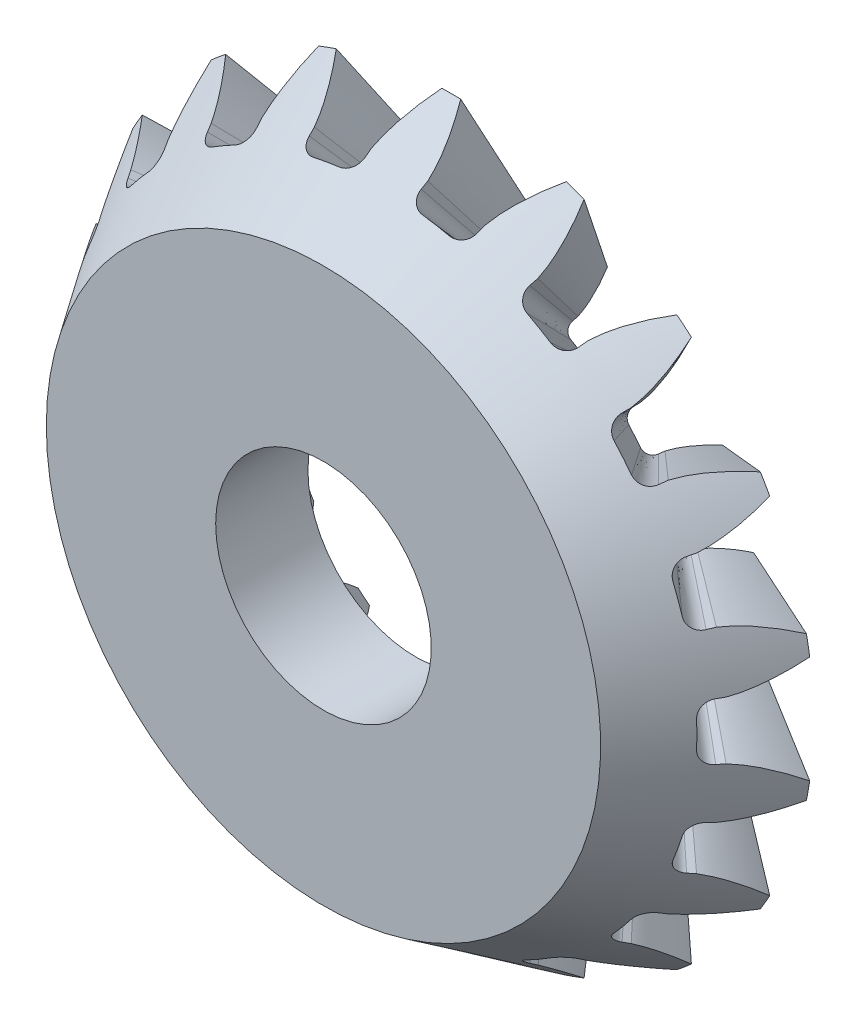
SolidWorks part; units mm, degrees
ref_plane "Front Plane" through (0, 0, 0) normal (0, 0, 1) x (1, 0, 0)
ref_plane "Top Plane" through (0, 0, 0) normal (0, 1, 0) x (1, 0, 0)
ref_plane "Right Plane" through (0, 0, 0) normal (1, 0, 0) x (0, 0, -1)
ref_axis "Gear Axis" through (0, 0, -1.3521) along (0, 0, 1)
sketch "Blank Sketch" plane through (0, 0, 0) normal (0, 1, 0) x (1, 0, 0)
  line L0 (0, 0) -> (0, -27.0416) construction
  line L1 (0, 0) -> (22.5, -15) construction
  line L2 (0, 0) -> (15.0115, -10.0077) construction
  line L3 (11.176, -15.7611) -> (15.6135, -9.1047)
  line L4 (15.6135, -9.1047) -> (23.5324, -13.4515)
  line L5 (23.5324, -13.4515) -> (17.9981, -21.7528)
  line L6 (17.9981, -21.7528) -> (7, -21.7528)
  line L7 (7, -21.7528) -> (7, -15.7611)
  line L8 (7, -15.7611) -> (11.176, -15.7611)
  line L9 (22.5, -15) -> (23.5324, -13.4515) construction
  line L10 (22.5, -15) -> (17.9981, -21.7528) construction
  line L11 (15.0115, -10.0077) -> (11.176, -15.7611) construction
  dimension "Axis" = 27.0416
  dimension "Cone" = 56.31
  dimension "Heel" = 27.0416
  dimension "Toe Cone" = 56.31
  dimension "Toe" = 18.0416
  dimension "Heel Square" = 90
  dimension "Addendum" = 1.8611
  dimension "Root Square" = 90
  dimension "Heel Rim" = 8.1158
  dimension "Toe Square" = 90
  dimension "Toe Rim" = 6.9147
  dimension "Front Square" = 90
  dimension "Face" = 4.927
  dimension "Back" = 10.9981
  dimension "Front" = 4.176
revolve "Blank" add sketch "Blank Sketch" angle 360 about L0
sketch "Cone Sketch" plane through (0, 0, 0) normal (0, 1, 0) x (1, 0, 0)
  line L0 (0, 0) -> (0, -27.0416) construction
  line L1 (0, 0) -> (24.5801, -16.3868)
  line L2 (0, 0) -> (12.9314, -8.6209)
  dimension "Axis" = 27.0416
  dimension "Toe Cone" = 56.31
  dimension "Heel Cone" = 56.31
  dimension "Heel" = 29.5416
  dimension "Toe" = 15.5416
ref_plane "Heel Plane" through (24.5801, 0, 16.3868) normal (0.8321, 0, 0.5547) x (0.5547, 0, -0.8321)
ref_plane "Toe Plane" through (12.9314, 0, 8.6209) normal (0.8321, 0, 0.5547) x (0.5547, 0, -0.8321)
sketch "Heel Section Sketch" plane through (24.5801, 0, 16.3868) normal (0.8321, 0, 0.5547) x (0.5547, 0, -0.8321)
  line L0 (0, 0) -> (-44.3125, 0) construction
  line L1 (-2.4361, 2.0543) -> (-2.9674, 2.0282)
  line L2 (-2.4361, -2.0543) -> (-2.9674, -2.0282)
  line L3 (4.4427, 5.6087) -> (4.4427, -5.6087)
  arc A0 (-2.9674, 2.0282) -> (-3.9541, 0.9668) centre (-2.9166, 0.9916) ccw
  arc A1 (-3.9541, -0.9668) -> (-2.9674, -2.0282) centre (-2.9166, -0.9916) ccw
  arc A2 (-3.9541, -0.9668) -> (-3.9541, 0.9668) centre (-44.3125, 0) ccw
  spline S0 degree 4 poles (-2.6291, 2.0265) (-2.5842, 2.0316) (-2.4741, 2.0474) (-2.3933, 2.0609) (-2.1776, 2.1023) (-2.0149, 2.1404) (-1.7927, 2.1952) (-1.5783, 2.2566) (-1.3413, 2.3286) (-1.1153, 2.4041) (-0.8853, 2.4853) (-0.6604, 2.5702) (-0.4261, 2.6632) (-0.1395, 2.7831) (0.2014, 2.935) (0.5903, 3.1201) (1.0229, 3.342) (1.4443, 3.5713) (1.8678, 3.8174) (2.2724, 4.0631) (2.6924, 4.335) (3.0718, 4.5879) (3.5028, 4.8948) (3.8332, 5.1342) (4.292, 5.4883) (4.5055, 5.6577) (4.7688, 5.8719) (4.9185, 5.9962) (4.989, 6.0556) (5.0278, 6.0882) (5.0475, 6.1048) knots 0 0 0 0 0 0.022117 0.039787 0.058126 0.081614 0.109122 0.13663 0.164138 0.191645 0.219153 0.246661 0.274169 0.305931 0.360947 0.415962 0.470978 0.525993 0.581009 0.636024 0.69104 0.746055 0.801071 0.856086 0.911102 0.955551 0.977775 0.988888 1 1 1 1 1 construction
  spline S1 degree 4 poles (-2.4361, 2.0543) (-2.4021, 2.06) (-2.3349, 2.0721) (-2.1776, 2.1023) (-2.0149, 2.1404) (-1.7927, 2.1952) (-1.5783, 2.2566) (-1.3413, 2.3286) (-1.1153, 2.4041) (-0.8853, 2.4853) (-0.6604, 2.5702) (-0.4261, 2.6632) (-0.1395, 2.7831) (0.2014, 2.935) (0.5903, 3.1201) (1.0229, 3.342) (1.4443, 3.5713) (1.8678, 3.8174) (2.2724, 4.0631) (2.6924, 4.335) (3.0718, 4.5879) (3.5028, 4.8948) (3.8332, 5.1342) (4.1946, 5.4131) (4.3587, 5.5418) (4.4427, 5.6087) knots 0.022117 0.022117 0.022117 0.022117 0.022117 0.039787 0.058126 0.081614 0.109122 0.13663 0.164138 0.191645 0.219153 0.246661 0.274169 0.305931 0.360947 0.415962 0.470978 0.525993 0.581009 0.636024 0.69104 0.746055 0.801071 0.856086 0.911102 0.911102 0.911102 0.911102 0.911102
  spline S2 degree 4 poles (-2.6291, -2.0265) (-2.5842, -2.0316) (-2.4741, -2.0474) (-2.3933, -2.0609) (-2.1776, -2.1023) (-2.0149, -2.1404) (-1.7927, -2.1952) (-1.5783, -2.2566) (-1.3413, -2.3286) (-1.1153, -2.4041) (-0.8853, -2.4853) (-0.6604, -2.5702) (-0.4261, -2.6632) (-0.1395, -2.7831) (0.2014, -2.935) (0.5903, -3.1201) (1.0229, -3.342) (1.4443, -3.5713) (1.8678, -3.8174) (2.2724, -4.0631) (2.6924, -4.335) (3.0718, -4.5879) (3.5028, -4.8948) (3.8332, -5.1342) (4.292, -5.4883) (4.5055, -5.6577) (4.7688, -5.8719) (4.9185, -5.9962) (4.989, -6.0556) (5.0278, -6.0882) (5.0475, -6.1048) knots 0 0 0 0 0 0.022117 0.039787 0.058126 0.081614 0.109122 0.13663 0.164138 0.191645 0.219153 0.246661 0.274169 0.305931 0.360947 0.415962 0.470978 0.525993 0.581009 0.636024 0.69104 0.746055 0.801071 0.856086 0.911102 0.955551 0.977775 0.988888 1 1 1 1 1 construction
  spline S3 degree 4 poles (-2.4361, -2.0543) (-2.4021, -2.06) (-2.3349, -2.0721) (-2.1776, -2.1023) (-2.0149, -2.1404) (-1.7927, -2.1952) (-1.5783, -2.2566) (-1.3413, -2.3286) (-1.1153, -2.4041) (-0.8853, -2.4853) (-0.6604, -2.5702) (-0.4261, -2.6632) (-0.1395, -2.7831) (0.2014, -2.935) (0.5903, -3.1201) (1.0229, -3.342) (1.4443, -3.5713) (1.8678, -3.8174) (2.2724, -4.0631) (2.6924, -4.335) (3.0718, -4.5879) (3.5028, -4.8948) (3.8332, -5.1342) (4.1946, -5.4131) (4.3587, -5.5418) (4.4427, -5.6087) knots 0.022117 0.022117 0.022117 0.022117 0.022117 0.039787 0.058126 0.081614 0.109122 0.13663 0.164138 0.191645 0.219153 0.246661 0.274169 0.305931 0.360947 0.415962 0.470978 0.525993 0.581009 0.636024 0.69104 0.746055 0.801071 0.856086 0.911102 0.911102 0.911102 0.911102 0.911102
  dimension "Root" = 40.3699
  dimension "Fillet" = 1.0378
  dimension "Centre" = 44.3125
sketch "Toe Section Sketch" plane through (12.9314, 0, 8.6209) normal (0.8321, 0, 0.5547) x (0.5547, 0, -0.8321)
  line L0 (0, 0) -> (-23.3125, 0) construction
  line L1 (-1.2816, 1.0807) -> (-1.5611, 1.067)
  line L2 (-1.2816, -1.0807) -> (-1.5611, -1.067)
  line L3 (2.3373, 2.9507) -> (2.3373, -2.9507)
  arc A0 (-1.5611, 1.067) -> (-2.0802, 0.5086) centre (-1.5344, 0.5217) ccw
  arc A1 (-2.0802, -0.5086) -> (-1.5611, -1.067) centre (-1.5344, -0.5217) ccw
  arc A2 (-2.0802, -0.5086) -> (-2.0802, 0.5086) centre (-23.3125, 0) ccw
  spline S0 degree 4 poles (-1.3857, 1.0656) (-1.3554, 1.0695) (-1.3037, 1.0768) (-1.2572, 1.0845) (-1.1474, 1.1057) (-1.0584, 1.1263) (-0.9443, 1.1547) (-0.8296, 1.1873) (-0.7061, 1.225) (-0.5865, 1.2648) (-0.4659, 1.3075) (-0.3473, 1.3522) (-0.2242, 1.4011) (-0.0733, 1.4642) (0.1059, 1.5441) (0.3106, 1.6415) (0.5381, 1.7582) (0.7598, 1.8788) (0.9826, 2.0083) (1.1955, 2.1376) (1.4164, 2.2806) (1.6161, 2.4137) (1.8427, 2.5751) (2.0167, 2.7011) (2.2578, 2.8872) (2.3846, 2.9878) (2.5448, 3.1185) (2.6148, 3.1774) (2.6547, 3.2111) knots 0 0 0 0 0 0.022117 0.039787 0.058126 0.081614 0.109122 0.13663 0.164138 0.191645 0.219153 0.246661 0.274169 0.305931 0.360947 0.415962 0.470978 0.525993 0.581009 0.636024 0.69104 0.746055 0.801071 0.856086 0.911102 0.955551 1 1 1 1 1 construction
  spline S1 degree 4 poles (-1.2816, 1.0807) (-1.2637, 1.0837) (-1.2275, 1.0903) (-1.1474, 1.1057) (-1.0584, 1.1263) (-0.9443, 1.1547) (-0.8296, 1.1873) (-0.7061, 1.225) (-0.5865, 1.2648) (-0.4659, 1.3075) (-0.3473, 1.3522) (-0.2242, 1.4011) (-0.0733, 1.4642) (0.1059, 1.5441) (0.3106, 1.6415) (0.5381, 1.7582) (0.7598, 1.8788) (0.9826, 2.0083) (1.1955, 2.1376) (1.4164, 2.2806) (1.6161, 2.4137) (1.8427, 2.5751) (2.0167, 2.7011) (2.2067, 2.8477) (2.2931, 2.9155) (2.3373, 2.9507) knots 0.022117 0.022117 0.022117 0.022117 0.022117 0.039787 0.058126 0.081614 0.109122 0.13663 0.164138 0.191645 0.219153 0.246661 0.274169 0.305931 0.360947 0.415962 0.470978 0.525993 0.581009 0.636024 0.69104 0.746055 0.801071 0.856086 0.911102 0.911102 0.911102 0.911102 0.911102
  spline S2 degree 4 poles (-1.3857, -1.0656) (-1.3554, -1.0695) (-1.3037, -1.0768) (-1.2572, -1.0845) (-1.1474, -1.1057) (-1.0584, -1.1263) (-0.9443, -1.1547) (-0.8296, -1.1873) (-0.7061, -1.225) (-0.5865, -1.2648) (-0.4659, -1.3075) (-0.3473, -1.3522) (-0.2242, -1.4011) (-0.0733, -1.4642) (0.1059, -1.5441) (0.3106, -1.6415) (0.5381, -1.7582) (0.7598, -1.8788) (0.9826, -2.0083) (1.1955, -2.1376) (1.4164, -2.2806) (1.6161, -2.4137) (1.8427, -2.5751) (2.0167, -2.7011) (2.2578, -2.8872) (2.3846, -2.9878) (2.5448, -3.1185) (2.6148, -3.1774) (2.6547, -3.2111) knots 0 0 0 0 0 0.022117 0.039787 0.058126 0.081614 0.109122 0.13663 0.164138 0.191645 0.219153 0.246661 0.274169 0.305931 0.360947 0.415962 0.470978 0.525993 0.581009 0.636024 0.69104 0.746055 0.801071 0.856086 0.911102 0.955551 1 1 1 1 1 construction
  spline S3 degree 4 poles (-1.2816, -1.0807) (-1.2637, -1.0837) (-1.2275, -1.0903) (-1.1474, -1.1057) (-1.0584, -1.1263) (-0.9443, -1.1547) (-0.8296, -1.1873) (-0.7061, -1.225) (-0.5865, -1.2648) (-0.4659, -1.3075) (-0.3473, -1.3522) (-0.2242, -1.4011) (-0.0733, -1.4642) (0.1059, -1.5441) (0.3106, -1.6415) (0.5381, -1.7582) (0.7598, -1.8788) (0.9826, -2.0083) (1.1955, -2.1376) (1.4164, -2.2806) (1.6161, -2.4137) (1.8427, -2.5751) (2.0167, -2.7011) (2.2067, -2.8477) (2.2931, -2.9155) (2.3373, -2.9507) knots 0.022117 0.022117 0.022117 0.022117 0.022117 0.039787 0.058126 0.081614 0.109122 0.13663 0.164138 0.191645 0.219153 0.246661 0.274169 0.305931 0.360947 0.415962 0.470978 0.525993 0.581009 0.636024 0.69104 0.746055 0.801071 0.856086 0.911102 0.911102 0.911102 0.911102 0.911102
  dimension "Root" = 21.2383
  dimension "Fillet" = 0.546
  dimension "Centre" = 23.3125
loft "Tooth Space" cut profiles "Heel Section Sketch", "Toe Section Sketch"
pattern_circular "Teeth" count 18 over 360 about axis through (0, 0, -1.3521) along (0, 0, 1) of "Tooth Space"
equation "\"No. of Teeth\"= 18"
equation "\"Module\"= 2.5"
equation "\"Bore Diameter\"= 14"
equation "\"Pressure Angle\"= 20"
equation "\"Shaft Angle\"= 90"
equation "\"Mate Teeth\"= 12"
equation "\"Pitch Cone Angle\"= IIF ( ( \"Mate Teeth\" / \"No. of Teeth\" + cos ( \"Shaft Angle\" ) ) > 0 , atn ( sin ( \"Shaft Angle\" ) / ( \"Mate Teeth\" / \"No. of Teeth\" + cos ( \"Shaft Angle\" ) ) ) , 180 + atn ( sin ( \"Shaft Angle\" ) / ( \"Mate Teeth\" / \"No. of Teeth\" + cos ( \"Shaft Angle\" ) ) ) )"
equation "\"Mate Cone Angle\"= \"Shaft Angle\" - \"Pitch Cone Angle\""
equation "\"Addendum\"= IIF ( \"No. of Teeth\" >= \"Mate Teeth\" , 0.54 * \"Module\" + 0.46 * \"Module\" / ( ( \"No. of Teeth\" * cos ( \"Mate Cone Angle\" ) ) / ( \"Mate Teeth\" * cos ( \"Pitch Cone Angle\" ) ) ) , 2 * \"Module\" - ( 0.54 * \"Module\" + 0.46 * \"Module\" / ( ( \"Mate Teeth\" * cos ( \"Pitch Cone Angle\" ) ) / ( \"No. of Teeth\" * cos ( \"Mate Cone Angle\" ) ) ) ) )"
equation "\"Outer Diameter\"= \"No. of Teeth\" * \"Module\" + 2 * \"Addendum\" * cos ( \"Pitch Cone Angle\" )"
equation "\"Pitch Diameter\"= \"No. of Teeth\" * \"Module\""
equation "\"Backlash\"= 0.3 * \"Module\""
equation "\"Arc Length\"= ( ( \"Module\" * pi ) / 2 + \"Backlash\" - 2 * ( \"Addendum\" - \"Module\" ) * tan ( \"Pressure Angle\" ) )"
equation "\"Fillet Radius\"= 0.38 * \"Module\""
equation "\"Mate Addendum\"= 2 * \"Module\" - \"Addendum\""
equation "\"Dedendum\"= 2.188 * \"Module\" - \"Addendum\""
equation "\"Tooth Depth\"= \"Addendum\" + \"Dedendum\""
equation "\"Mate Dedendum\"= 2.188 * \"Module\" - \"Mate Addendum\""
equation "\"Face Width\"= 9"
equation "\"Cone Distance\"= \"Pitch Diameter\" / ( 2 * sin ( \"Pitch Cone Angle\" ) )"
equation "\"Dedendum Angle\"= atn ( \"Dedendum\" / \"Cone Distance\" )"
equation "\"Mate Dedendum Angle\"= atn ( \"Mate Dedendum\" / \"Cone Distance\" )"
equation "\"Face Angle\"= \"Pitch Cone Angle\" + \"Mate Dedendum Angle\""
equation "\"Root Angle\"= \"Pitch Cone Angle\" - \"Dedendum Angle\""
equation "\"Overrun\"= \"Module\""
equation "\"Back Cone Pitch Diameter\"= \"Pitch Diameter\" / cos ( \"Pitch Cone Angle\" )"
equation "\"Back Cone Outer Diameter\"= \"Back Cone Pitch Diameter\" + 2 * \"Addendum\""
equation "\"Root Diameter\"= \"Back Cone Outer Diameter\" - 2 * \"Tooth Depth\""
equation "\"Base Diameter\"= \"Back Cone Pitch Diameter\" * cos ( \"Pressure Angle\" )"
equation "\"Base Radius\"= \"Base Diameter\" / 2"
equation "\"Tooth Thickness\"= \"Module\" * pi - \"Arc Length\""
equation "\"Half Space Angle\"= ( \"Arc Length\" / \"Back Cone Pitch Diameter\" ) * 180 / pi"
equation "\"Involute Fn\"= tan ( \"Pressure Angle\" ) - \"Pressure Angle\" * pi / 180"
equation "\"Flank Offset\"= \"Arc Length\" / \"Back Cone Pitch Diameter\" - \"Involute Fn\""
equation "\"Tip Cap Diameter\"= \"Back Cone Outer Diameter\" + 2 * \"Module\""
equation "\"Flank Start Diameter\"= IIF ( \"Base Diameter\" >= ( \"Root Diameter\" + 3 * \"Fillet Radius\" ) , \"Base Diameter\" , \"Root Diameter\" + 3 * \"Fillet Radius\" )"
equation "\"Involute t1\"= ( abs ( ( \"Flank Start Diameter\" / \"Base Diameter\" ) ^ 2 - 1 ) ) ^ 0.5"
equation "\"Involute t2\"= ( abs ( ( \"Tip Cap Diameter\" / \"Base Diameter\" ) ^ 2 - 1 ) ) ^ 0.5"
equation "\"Flank Arc Radius\"= ( \"Back Cone Pitch Diameter\" / 2 ) * sin ( \"Pressure Angle\" )"
equation "\"Flank Centre Angle\"= \"Half Space Angle\" + \"Pressure Angle\""
equation "\"Heel Distance\"= \"Cone Distance\" + \"Overrun\""
equation "\"Toe Distance\"= \"Cone Distance\" - \"Face Width\" - \"Overrun\""
equation "\"Heel Scale\"= \"Heel Distance\" / \"Cone Distance\""
equation "\"Toe Scale\"= \"Toe Distance\" / \"Cone Distance\""
equation "\"Heel Virtual Radius\"= \"Heel Distance\" * tan ( \"Pitch Cone Angle\" )"
equation "\"Toe Virtual Radius\"= \"Toe Distance\" * tan ( \"Pitch Cone Angle\" )"
equation "\"Axis@Blank Sketch\"= \"Cone Distance\""
equation "\"Cone@Blank Sketch\"= \"Pitch Cone Angle\""
equation "\"Heel@Blank Sketch\"= \"Cone Distance\""
equation "\"Toe Cone@Blank Sketch\"= \"Pitch Cone Angle\""
equation "\"Toe@Blank Sketch\"= \"Cone Distance\" - \"Face Width\""
equation "\"Addendum@Blank Sketch\"= \"Addendum\""
equation "\"Heel Rim@Blank Sketch\"= \"Dedendum\" + \"Module\" / cos ( \"Pitch Cone Angle\" )"
equation "\"Toe Rim@Blank Sketch\"= \"Dedendum\" - \"Face Width\" * tan ( \"Dedendum Angle\" ) + \"Module\" / cos ( \"Pitch Cone Angle\" )"
equation "\"Face@Blank Sketch\"= \"Mate Dedendum Angle\""
equation "\"Back@Blank Sketch\"= \"Cone Distance\" * sin ( \"Pitch Cone Angle\" ) - \"Dedendum\" * cos ( \"Pitch Cone Angle\" ) - \"Module\" - \"Bore Diameter\" / 2"
equation "\"Front@Blank Sketch\"= ( \"Cone Distance\" - \"Face Width\" ) * sin ( \"Pitch Cone Angle\" ) - ( \"Dedendum\" - \"Face Width\" * tan ( \"Dedendum Angle\" ) + \"Module\" / cos ( \"Pitch Cone Angle\" ) ) * cos ( \"Pitch Cone Angle\" ) - \"Bore Diameter\" / 2"
equation "\"Axis@Cone Sketch\"= \"Cone Distance\""
equation "\"Heel Cone@Cone Sketch\"= \"Pitch Cone Angle\""
equation "\"Heel@Cone Sketch\"= \"Heel Distance\""
equation "\"Toe Cone@Cone Sketch\"= \"Pitch Cone Angle\""
equation "\"Toe@Cone Sketch\"= \"Toe Distance\""
equation "\"Centre@Heel Section Sketch\"= \"Heel Virtual Radius\""
equation "\"Root@Heel Section Sketch\"= ( \"Root Diameter\" / 2 ) * \"Heel Scale\""
equation "\"Fillet@Heel Section Sketch\"= ( \"Fillet Radius\" ) * \"Heel Scale\""
equation "\"Centre@Toe Section Sketch\"= \"Toe Virtual Radius\""
equation "\"Root@Toe Section Sketch\"= ( \"Root Diameter\" / 2 ) * \"Toe Scale\""
equation "\"Fillet@Toe Section Sketch\"= ( \"Fillet Radius\" ) * \"Toe Scale\""
equation "\"Count@Teeth\"= \"No. of Teeth\""
